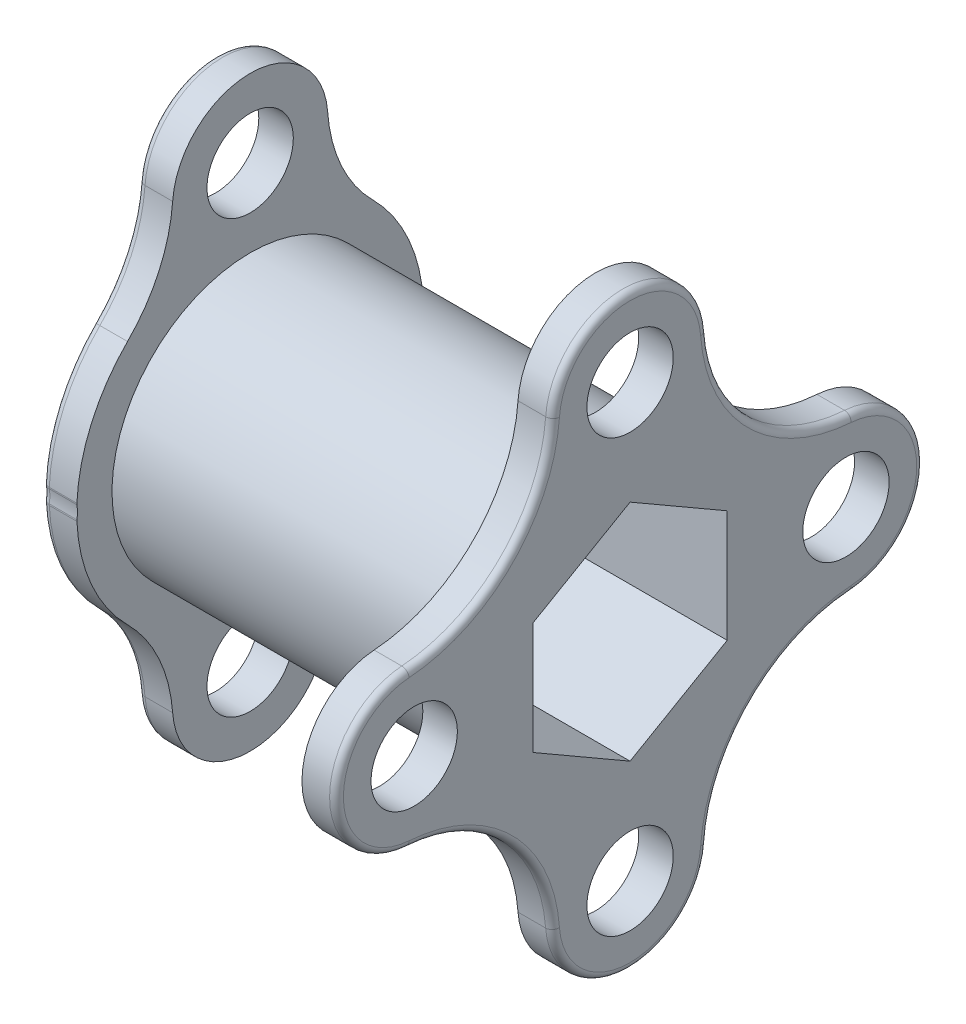
SolidWorks part; units mm, degrees
ref_plane "Front Plane" through (0, 0, 0) normal (0, 0, 1) x (1, 0, 0)
ref_plane "Top Plane" through (0, 0, 0) normal (0, 1, 0) x (1, 0, 0)
ref_plane "Right Plane" through (0, 0, 0) normal (1, 0, 0) x (0, 0, -1)
sketch "Sketch1" plane through (0, 0, 0) normal (1, 0, 0) x (0, 0, -1)
  line L0 (0, 8.2489) -> (0, -8.2489) construction
  line L1 (7.1438, 4.1244) -> (-7.1438, -4.1244) construction
  line L2 (-7.1438, 4.1244) -> (7.1438, -4.1244) construction
  line L3 (0, 21.59) -> (0, 10.16) construction
  line L4 (-15.875, 0) -> (15.875, 0) construction
  line L5 (0, 15.875) -> (0, -15.875) construction
  line L12 (7.1438, 4.1244) -> (0, 8.2489)
  line L13 (0, 8.2489) -> (-7.1438, 4.1244)
  line L14 (-7.1438, 4.1244) -> (-7.1438, -4.1244)
  line L15 (-7.1438, -4.1244) -> (0, -8.2489)
  line L16 (0, -8.2489) -> (7.1438, -4.1244)
  line L17 (7.1438, -4.1244) -> (7.1438, 4.1244)
  circle A0 centre (0, 0) radius 10.16
  circle A2 centre (0, 15.875) radius 3.175
  circle A3 centre (15.875, 0) radius 3.175
  circle A4 centre (0, -15.875) radius 3.175
  circle A5 centre (-15.875, 0) radius 3.175
  arc A6 (5.7004, 16.2837) -> (-5.7004, 16.2837) centre (0, 15.875) ccw
  arc A7 (-16.2837, 5.7004) -> (-16.2837, -5.7004) centre (-15.875, 0) ccw
  arc A8 (-5.7004, -16.2837) -> (5.7004, -16.2837) centre (0, -15.875) ccw
  arc A9 (16.2837, -5.7004) -> (16.2837, 5.7004) centre (15.875, 0) ccw
  arc A10 (-5.7004, 16.2837) -> (-16.2837, 5.7004) centre (-17.1011, 17.1011) cw
  arc A11 (16.2837, 5.7004) -> (5.7004, 16.2837) centre (17.1011, 17.1011) cw
  arc A12 (5.7004, -16.2837) -> (16.2837, -5.7004) centre (17.1011, -17.1011) cw
  arc A13 (-16.2837, -5.7004) -> (-5.7004, -16.2837) centre (-17.1011, -17.1011) cw
  circle A14 centre (0, 15.875) radius 5.715 construction
  circle A15 centre (-15.875, 0) radius 5.715 construction
  circle A16 centre (0, -15.875) radius 5.715 construction
  circle A17 centre (15.875, 0) radius 5.715 construction
  arc A19 (-9.0189, 9.0189) -> (-9.0189, -9.0189) centre (0, 0) ccw
  arc A20 (0.5255, 12.7438) -> (-0.5255, 12.7438) centre (0, 0) ccw
  arc A21 (9.0189, -9.0189) -> (9.0189, 9.0189) centre (0, 0) ccw
  arc A22 (-0.5255, -12.7438) -> (0.5255, -12.7438) centre (0, 0) ccw
  point P23 (0, 0)
  point P28 (-9.0189, 9.0189)
  point P42 (0, 0)
  point P49 (0, 0)
  dimension "D2" = 20.32
  dimension "D3" = 11.43
  dimension "D7" = 6.35
  dimension "D1" = 8.2489
  dimension "D4" = 60
  dimension "D5" = 60
  dimension "D6" = 60
  dimension "D10" = 31.75
  dimension "D9" = 2.54
  dimension "D8" = 4
  dimension "D11" = 4
extrude "Boss-Extrude4" add sketch "Sketch1" along normal blind 2.54 contours A19 A10 A7 A13 A5 | A3 A21 A11 A6 A10 A19 A5 A13 A8 A12 A0 A2 A4 | A0 L17 L16 L15 L14 L13 L12 | A21 A3 A12 A9 A11 region at (0, 0, 9.8726) region at (0, 3.3831, -16.1569) region at (0, 0, -12.1986) region at (0, 5.211, 11.882)
extrude "Boss-Extrude5" add sketch "Sketch1<7>" against normal up to surface (25.4 mm away) contours A0 L17 L16 L15 L14 L13 L12 region at (0, 0, 9.8726)
sketch "Sketch1<7>" plane through (0, 0, 0) normal (1, 0, 0) x (0, 0, -1) same geometry as "Sketch1"
extrude "Boss-Extrude7" add sketch "Sketch1<9>" against normal blind 2.54 from surface contours A0 L17 L16 L15 L14 L13 L12 | A3 A21 A11 A6 A10 A19 A5 A13 A8 A12 A0 A2 A4 region at (0, 0, 9.8726) region at (0, 0, -12.1986) starting at face at (-25.4, 10.16, 0)
sketch "Sketch1<9>" plane through (0, 0, 0) normal (1, 0, 0) x (0, 0, -1) same geometry as "Sketch1"
fillet "Fillet1" radius 0.508 8 edges at (2.54, 9.0189, -9.0189) (2.54, 0, -21.59) (2.54, -9.0189, -9.0189) (2.54, -21.59, 0) (2.54, -9.0189, 9.0189) (2.54, 0, 21.59) (2.54, 9.0189, 9.0189) (2.54, 21.59, 0)
fillet "Fillet2" radius 0.508 4 edges at (-26.67, -0.5255, 12.7438) (-26.67, 0.5255, 12.7438) (-26.67, -0.5255, -12.7438) (-26.67, 0.5255, -12.7438)
fillet "Fillet3" radius 0.508 16 edges at (-27.94, 12.352, 6.7044) (-27.94, 21.59, 0) (-27.94, 12.352, -6.7044) (-27.94, 5.1467, -11.6701) (-27.94, 0.528, -12.7413) (-27.94, 0, -12.7) (-27.94, -0.528, -12.7413) (-27.94, -5.1467, -11.6701) (-27.94, -12.352, -6.7044) (-27.94, -21.59, 0) (-27.94, -12.352, 6.7044) (-27.94, -5.1467, 11.6701) (-27.94, -0.528, 12.7413) (-27.94, 0, 12.7) (-27.94, 0.528, 12.7413) (-27.94, 5.1467, 11.6701)
